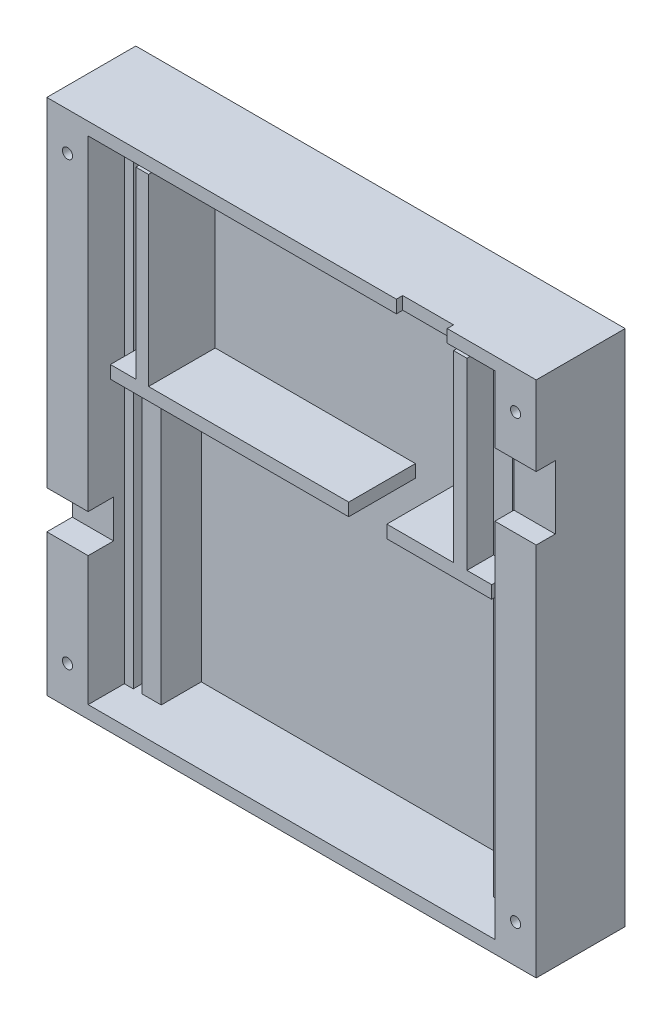
SolidWorks part; units mm, degrees
ref_plane "Front Plane" through (0, 0, 0) normal (1, 0, 0) x (0, 1, 0)
ref_plane "Top Plane" through (0, 0, 0) normal (0, 0, 1) x (0, 1, 0)
ref_plane "Right Plane" through (0, 0, 0) normal (0, 1, 0) x (-1, 0, 0)
sketch "Sketch1" plane through (0, 0, 0) normal (0, 0, 1) x (0, 1, 0)
  line L1 (0, 0) -> (81.5, 0)
  line L2 (0, 0) -> (0, -77)
  line L3 (0, -77) -> (81.5, -77)
  line L4 (81.5, 0) -> (81.5, -77)
extrude "Boss-Extrude1" add sketch "Sketch1" along normal blind 2
sketch "Sketch2" plane through (0, 0, 0) normal (0, 0, 1) x (0, 1, 0)
  line L0 (81.5, -77) -> (81.5, 0) construction
  line L1 (0, 0) -> (81.5, 0)
  line L2 (0, 0) -> (0, -6.5)
  line L3 (0, -6.5) -> (81.5, -6.5)
  line L4 (81.5, 0) -> (81.5, -6.5)
extrude "Boss-Extrude2" add sketch "Sketch2" along normal blind 10
sketch "Sketch3" plane through (0, 0, 0) normal (0, 0, 1) x (0, 1, 0)
  line L0 (0, -6.5) -> (81.5, -6.5) construction
  line L1 (0, 0) -> (22.3, 0)
  line L2 (0, 0) -> (0, -6.5)
  line L3 (0, -6.5) -> (22.3, -6.5)
  line L4 (22.3, 0) -> (22.3, -6.5)
extrude "Boss-Extrude3" add sketch "Sketch3" along normal blind 14
sketch "Sketch4" plane through (0, 0, 0) normal (0, 0, 1) x (0, 1, 0)
  line L0 (81.5, 0) -> (22.3, 0) construction
  line L1 (28.3, 0) -> (81.5, 0)
  line L2 (28.3, 0) -> (28.3, -6.5)
  line L3 (28.3, -6.5) -> (81.5, -6.5)
  line L4 (81.5, 0) -> (81.5, -6.5)
extrude "Boss-Extrude4" add sketch "Sketch4" along normal blind 14
sketch "Sketch5" plane through (0, 0, 0) normal (0, 0, 1) x (0, 1, 0)
  line L0 (0, -6.5) -> (0, -77) construction
  line L1 (0, -70.5) -> (81.5, -70.5)
  line L2 (0, -70.5) -> (0, -77)
  line L3 (0, -77) -> (81.5, -77)
  line L4 (81.5, -70.5) -> (81.5, -77)
extrude "Boss-Extrude5" add sketch "Sketch5" along normal blind 11
sketch "Sketch6" plane through (0, 0, 0) normal (0, 0, 1) x (0, 1, 0)
  line L0 (0, -77) -> (81.5, -77) construction
  line L1 (0, -70.5) -> (59, -70.5)
  line L2 (0, -70.5) -> (0, -77)
  line L3 (0, -77) -> (59, -77)
  line L4 (59, -70.5) -> (59, -77)
extrude "Boss-Extrude6" add sketch "Sketch6" along normal blind 14
sketch "Sketch7" plane through (0, 0, 0) normal (0, 0, 1) x (0, 1, 0)
  line L0 (0, -70.5) -> (81.5, -70.5) construction
  line L1 (69, -70.5) -> (81.5, -70.5)
  line L2 (69, -70.5) -> (69, -77)
  line L3 (69, -77) -> (81.5, -77)
  line L4 (81.5, -70.5) -> (81.5, -77)
extrude "Boss-Extrude7" add sketch "Sketch7" along normal blind 14
sketch "Sketch8" plane through (0, 0, 0) normal (0, 0, 1) x (0, 1, 0)
  line L0 (0, -70.5) -> (81.5, -70.5) construction
  line L1 (0, -6.5) -> (2, -6.5)
  line L2 (0, -6.5) -> (0, -70.5)
  line L3 (0, -70.5) -> (2, -70.5)
  line L4 (2, -6.5) -> (2, -70.5)
extrude "Boss-Extrude8" add sketch "Sketch8" along normal blind 14
sketch "Sketch9" plane through (0, 0, 0) normal (0, 0, 1) x (0, 1, 0)
  line L0 (28.3, -6.5) -> (81.5, -6.5) construction
  line L1 (79.5, -6.5) -> (81.5, -6.5)
  line L2 (79.5, -6.5) -> (79.5, -70.5)
  line L3 (79.5, -70.5) -> (81.5, -70.5)
  line L4 (81.5, -6.5) -> (81.5, -70.5)
extrude "Boss-Extrude9" add sketch "Sketch9" along normal blind 13
sketch "Sketch10" plane through (0, 0, 0) normal (0, 0, 1) x (0, 1, 0)
  line L0 (28.3, -6.5) -> (81.5, -6.5) construction
  line L1 (79.5, -6.5) -> (81.5, -6.5)
  line L2 (79.5, -6.5) -> (79.5, -55)
  line L3 (79.5, -55) -> (81.5, -55)
  line L4 (81.5, -6.5) -> (81.5, -55)
  line L5 (81.5, -70.5) -> (81.5, -6.5) construction
extrude "Boss-Extrude10" add sketch "Sketch10" along normal blind 14
sketch "Sketch11" plane through (0, 0, 0) normal (0, 0, 1) x (0, 1, 0)
  line L0 (79.5, -70.5) -> (79.5, -6.5) construction
  line L1 (79.5, -63) -> (81.5, -63)
  line L2 (79.5, -63) -> (79.5, -70.5)
  line L3 (79.5, -70.5) -> (81.5, -70.5)
  line L4 (81.5, -63) -> (81.5, -70.5)
extrude "Boss-Extrude11" add sketch "Sketch11" along normal blind 14
sketch "Sketch12" plane through (0, 0, 0) normal (0, 0, 1) x (0, 1, 0)
  line L0 (79.5, -70.5) -> (79.5, -6.5) construction
  line L1 (2, -6.5) -> (79.5, -6.5)
  line L2 (2, -6.5) -> (2, -7.9)
  line L3 (2, -7.9) -> (79.5, -7.9)
  line L4 (79.5, -6.5) -> (79.5, -7.9)
extrude "Boss-Extrude12" add sketch "Sketch12" along normal blind 8.3
sketch "Sketch13" plane through (0, 0, 0) normal (0, 0, 1) x (0, 1, 0)
  line L0 (2, -70.5) -> (2, -6.5) construction
  line L1 (2, -9.3) -> (79.5, -9.3)
  line L2 (2, -9.3) -> (2, -12.3)
  line L3 (2, -12.3) -> (79.5, -12.3)
  line L4 (79.5, -9.3) -> (79.5, -12.3)
  line L5 (79.5, -70.5) -> (79.5, -7.9) construction
extrude "Boss-Extrude13" add sketch "Sketch13" along normal blind 8.3
sketch "Sketch14" plane through (0, 0, 0) normal (0, 0, 1) x (0, 1, 0)
  line L0 (2, -70.5) -> (2, -6.5) construction
  line L1 (2, -64.6) -> (79.5, -64.6)
  line L2 (2, -64.6) -> (2, -67.6)
  line L3 (2, -67.6) -> (79.5, -67.6)
  line L4 (79.5, -64.6) -> (79.5, -67.6)
  line L5 (79.5, -70.5) -> (79.5, -12.3) construction
extrude "Boss-Extrude14" add sketch "Sketch14" along normal blind 8.3
sketch "Sketch15" plane through (0, 0, 0) normal (0, 0, 1) x (0, 1, 0)
  line L0 (2, -70.5) -> (2, -6.5) construction
  line L1 (2, -69) -> (79.5, -69)
  line L2 (2, -69) -> (2, -70.5)
  line L3 (2, -70.5) -> (79.5, -70.5)
  line L4 (79.5, -69) -> (79.5, -70.5)
extrude "Boss-Extrude15" add sketch "Sketch15" along normal blind 8.3
sketch "Sketch16" plane through (0, 0, 0) normal (0, 0, 1) x (0, 1, 0)
  line L1 (46.6, -8.5) -> (48.6, -8.5)
  line L2 (46.6, -8.5) -> (46.6, -46)
  line L3 (46.6, -46) -> (48.6, -46)
  line L4 (48.6, -8.5) -> (48.6, -46)
extrude "Boss-Extrude16" add sketch "Sketch16" along normal blind 12.5
sketch "Sketch17" plane through (0, 0, 0) normal (0, 0, 1) x (0, 1, 0)
  line L1 (46.6, -52) -> (48.6, -52)
  line L2 (46.6, -52) -> (46.6, -68.5)
  line L3 (46.6, -68.5) -> (48.6, -68.5)
  line L4 (48.6, -52) -> (48.6, -68.5)
extrude "Boss-Extrude17" add sketch "Sketch17" along normal blind 12.5
sketch "Sketch18" plane through (0, 0, 0) normal (0, 0, 1) x (0, 1, 0)
  line L0 (48.6, -46) -> (48.6, -8.5) construction
  line L1 (48.6, -12.5) -> (77.5, -12.5)
  line L2 (48.6, -12.5) -> (48.6, -14.5)
  line L3 (48.6, -14.5) -> (77.5, -14.5)
  line L4 (77.5, -12.5) -> (77.5, -14.5)
extrude "Boss-Extrude18" add sketch "Sketch18" along normal blind 12.5
sketch "Sketch19" plane through (0, 0, 0) normal (0, 0, 1) x (0, 1, 0)
  line L0 (48.6, -68.5) -> (48.6, -52) construction
  line L1 (48.6, -62.5) -> (77.5, -62.5)
  line L2 (48.6, -62.5) -> (48.6, -64.6)
  line L3 (48.6, -64.6) -> (77.5, -64.6)
  line L4 (77.5, -62.5) -> (77.5, -64.6)
  line L5 (48.6, -64.6) -> (79.5, -64.6) construction
extrude "Boss-Extrude19" add sketch "Sketch19" along normal blind 12.5
sketch "Sketch20" plane through (0, 0, 0) normal (0, 0, 1) x (0, 1, 0)
  circle A0 centre (6, -3.25) radius 0.8
extrude "Cut-Extrude1" cut sketch "Sketch20" along normal blind 20
sketch "Sketch21" plane through (0, 0, 0) normal (0, 0, 1) x (0, 1, 0)
  circle A0 centre (75.5, -3.25) radius 0.8
extrude "Cut-Extrude2" cut sketch "Sketch21" along normal blind 20
sketch "Sketch22" plane through (0, 0, 0) normal (0, 0, 1) x (0, 1, 0)
  circle A0 centre (6, -73.75) radius 0.8
extrude "Cut-Extrude3" cut sketch "Sketch22" along normal blind 20
sketch "Sketch23" plane through (0, 0, 0) normal (0, 0, 1) x (0, 1, 0)
  circle A0 centre (75.5, -73.75) radius 0.8
extrude "Cut-Extrude4" cut sketch "Sketch23" along normal blind 20
